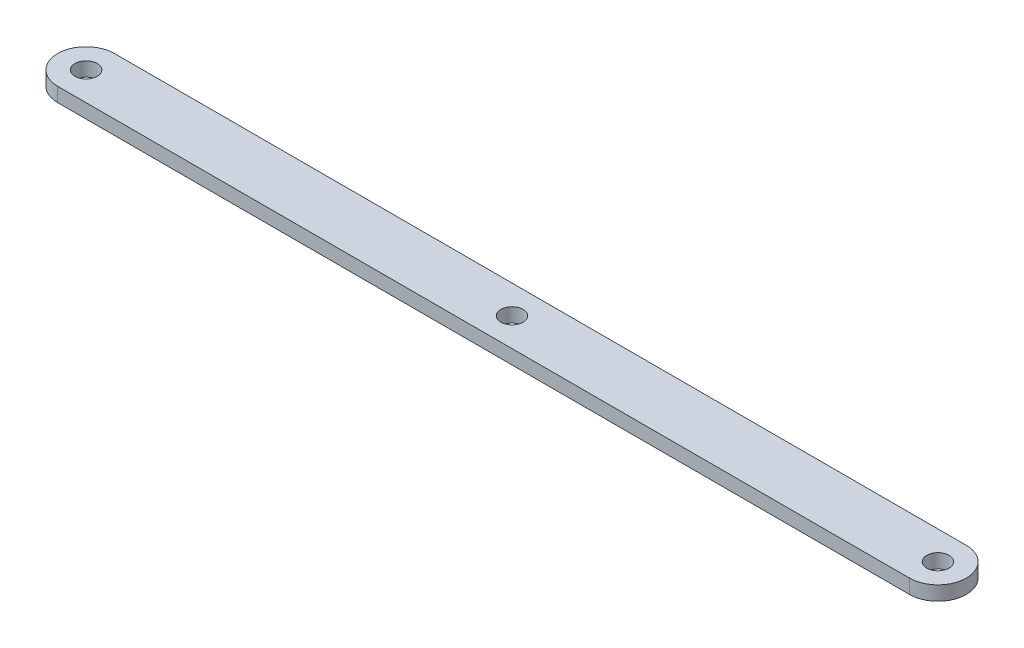
SolidWorks part; units mm, degrees
ref_plane "Front Plane" through (0, 0, 0) normal (0, 0, 1) x (1, 0, 0)
ref_plane "Top Plane" through (0, 0, 0) normal (0, 1, 0) x (1, 0, 0)
ref_plane "Right Plane" through (0, 0, 0) normal (1, 0, 0) x (0, 0, -1)
sketch "Sketch1" plane through (0, 0, 0) normal (0, 1, 0) x (1, 0, 0)
  line L0 (-95.25, 0) -> (95.25, 0) construction
  line L1 (-95.25, 6.35) -> (95.25, 6.35)
  line L2 (-95.25, -6.35) -> (95.25, -6.35)
  arc A0 (-95.25, 6.35) -> (-95.25, -6.35) centre (-95.25, 0) ccw
  arc A1 (95.25, -6.35) -> (95.25, 6.35) centre (95.25, 0) ccw
  circle A2 centre (95.25, 0) radius 2.5797 construction
  circle A3 centre (-95.25, 0) radius 2.5797 construction
  circle A4 centre (0, 0) radius 2.5797 construction
  point P3 (0, 0)
  dimension "D2" = 6.35
  dimension "D3" = 5.1594
  dimension "D1" = 190.5
extrude "Boss-Extrude1" add sketch "Sketch1" along normal blind 3.175
hole_wizard "#10 Clearance Hole1" positions "Sketch2" profile "Sketch3" hole size "#10" standard "ANSI Inch" end condition through all
sketch "Sketch2" plane through (0, 3.175, 0) normal (0, 1, 0) x (1, 0, 0)
  line L0 (95.25, 0) -> (-95.25, 0) construction
  point P0 (-95.25, 0)
  point P2 (0, 0)
  point P5 (95.25, 0)
  dimension "D1" = 190.5
sketch "Sketch3" plane through (-95.25, 3.175, 0) normal (1, 0, 0) x (0, 0, 1)
  line L0 (0, 0) -> (0, 3.175)
  line L1 (0, 3.175) -> (2.4892, 3.175)
  line L2 (2.4892, 3.175) -> (2.4892, 0)
  line L5 (2.4892, 0) -> (0, 0)
  line L11 (0, -6.35) -> (0, 107.95) construction
  dimension "Thru Hole Dia." = 4.9784
  dimension "Thru Hole Depth" = 3.175
